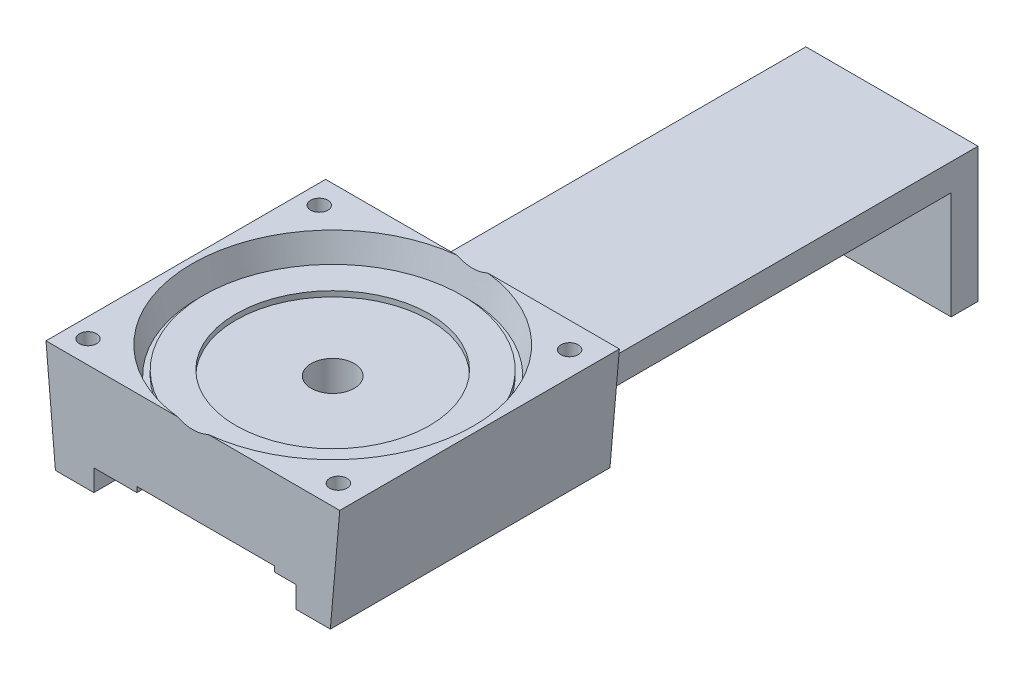
SolidWorks part; units mm, degrees
material "1060 Alloy"
ref_plane "Front Plane" through (0, 0, 0) normal (0, 0, 1) x (1, 0, 0)
ref_plane "Top Plane" through (0, 0, 0) normal (0, 1, 0) x (1, 0, 0)
ref_plane "Right Plane" through (0, 0, 0) normal (1, 0, 0) x (0, 0, -1)
sketch "Sketch1" plane through (0, 0, 0) normal (0, 1, 0) x (1, 0, 0)
  line L0 (-22.225, 41.275) -> (-41.275, 41.275)
  line L1 (41.275, -41.275) -> (-41.275, -41.275)
  line L2 (41.275, -41.275) -> (41.275, 41.275)
  line L3 (41.275, 41.275) -> (28.575, 41.275)
  line L4 (-41.275, -41.275) -> (-41.275, 41.275)
  line L5 (41.275, -41.275) -> (-41.275, 41.275) construction
  line L6 (41.275, 41.275) -> (-41.275, -41.275) construction
  line L8 (-22.225, 41.275) -> (-22.225, 161.925)
  line L9 (-22.225, 161.925) -> (28.575, 161.925)
  line L10 (28.575, 41.275) -> (28.575, 161.925)
  point P0 (0, 0)
  dimension "D1" = 82.55
  dimension "D2" = 82.55
  dimension "D3" = 50.8
  dimension "D4" = 12.7
  dimension "D5" = 203.2
extrude "Boss-Extrude1" add sketch "Sketch1" against normal blind 7.9375
sketch "Sketch2" plane through (0, -7.9375, 0) normal (0, -1, 0) x (1, 0, 0)
  line L0 (28.575, -41.275) -> (28.575, -161.925) construction
  line L1 (-22.225, -161.925) -> (28.575, -161.925)
  line L2 (-22.225, -161.925) -> (-22.225, -153.9875)
  line L3 (-22.225, -153.9875) -> (28.575, -153.9875)
  line L4 (28.575, -161.925) -> (28.575, -153.9875)
  dimension "D1" = 7.9375
extrude "Boss-Extrude2" add sketch "Sketch2" along normal blind 31.75
sketch "Sketch8" plane through (0, 0, 0) normal (0, 1, 0) x (1, 0, 0)
  line L1 (-41.275, -41.275) -> (41.275, -41.275)
  line L2 (-41.275, -41.275) -> (-41.275, 41.275)
  line L3 (-41.275, 41.275) -> (41.275, 41.275)
  line L4 (41.275, -41.275) -> (41.275, 41.275)
extrude "Boss-Extrude6" add sketch "Sketch8" along normal blind 7.9375
sketch "Sketch3" plane through (0, -7.9375, 0) normal (0, -1, 0) x (1, 0, 0)
  line L0 (-22.225, -41.275) -> (-41.275, -41.275) construction
  line L1 (-41.275, 41.275) -> (-29.0692, 41.275)
  line L2 (-41.275, 41.275) -> (-41.275, -41.275)
  line L3 (-41.275, -41.275) -> (-29.0692, -41.275)
  line L4 (-29.0692, 41.275) -> (-29.0692, -41.275)
  line L6 (41.275, 41.275) -> (28.575, 41.275)
  line L7 (41.275, 41.275) -> (41.275, -41.275)
  line L8 (41.275, -41.275) -> (28.575, -41.275)
  line L9 (28.575, 41.275) -> (28.575, -41.275)
extrude "Boss-Extrude3" [suppressed] add sketch "Sketch3" along normal blind 7.9375
sketch "Sketch4" plane through (0, 0, 0) normal (0, 1, 0) x (1, 0, 0)
  circle A0 centre (0, 0) radius 6.35
  dimension "D1" = 12.7
extrude "Cut-Extrude1" [suppressed] cut sketch "Sketch4" against normal through all
sketch "Sketch5" [suppressed] plane through (0, -7.9375, 0) normal (0, -1, 0) x (1, 0, 0)
  line L1 (-29.0692, 41.275) -> (-16.3692, 41.275)
  line L2 (-29.0692, 41.275) -> (-29.0692, -41.275)
  line L3 (-29.0692, -41.275) -> (-16.3692, -41.275)
  line L4 (-16.3692, 41.275) -> (-16.3692, -41.275)
  line L5 (28.575, 41.275) -> (22.225, 41.275)
  line L6 (28.575, 41.275) -> (28.575, -41.275)
  line L7 (28.575, -41.275) -> (22.225, -41.275)
  line L8 (22.225, 41.275) -> (22.225, -41.275)
  dimension "D1" = 12.7
  dimension "D2" = 82.55
  dimension "D3" = 6.35
  dimension "D4" = 82.55
extrude "Boss-Extrude4" [suppressed] add sketch "Sketch5" along normal blind 1.5875
sketch "Sketch6" plane through (0, 0, 0) normal (0, 1, 0) x (1, 0, 0)
  circle A0 centre (0, 0) radius 28.575
  circle A1 centre (0, 0) radius 38.1
  dimension "D1" = 57.15
  dimension "D2" = 76.2
extrude "Boss-Extrude5" [suppressed] add sketch "Sketch6" along normal blind 1.5875
draft "Draft1" [suppressed] type of draft neutral plane draft angle 5 neutral plane "Top Plane" faces to draft 4 parameters "D1"=5
draft "Draft2" [suppressed] type of draft neutral plane draft angle 5 faces to draft 1 parameters "D1"=5
sketch "Sketch9" plane through (0, -7.9375, 0) normal (0, -1, 0) x (-1, 0, 0)
  line L0 (41.275, 41.275) -> (-41.275, 41.275) construction
  line L1 (-41.275, 41.275) -> (-41.275, -41.275) construction
  line L2 (-41.275, -41.275) -> (41.275, -41.275) construction
  line L3 (41.275, -41.275) -> (41.275, 41.275) construction
  line L4 (41.275, 41.275) -> (-41.275, 41.275)
  line L5 (-41.275, 41.275) -> (-41.275, -41.275)
  line L6 (-41.275, -41.275) -> (41.275, -41.275)
  line L7 (41.275, -41.275) -> (41.275, 41.275)
sketch "Sketch10" plane through (0, 7.9375, 0) normal (0, 1, 0) x (1, 0, 0)
  circle A0 centre (0, 0) radius 6.35
  dimension "D1" = 12.7
extrude "Center Hole" cut sketch "Sketch10" against normal up to surface (15.875 mm away) up to face at (1.5875, -7.9375, -48.8156)
sketch "Sketch12" plane through (0, -7.9375, 0) normal (0, -1, 0) x (1, 0, 0)
  line L0 (-41.275, -41.275) -> (41.275, -41.275) construction
  line L1 (-41.275, 41.275) -> (-29.2318, 41.275)
  line L2 (-41.275, 41.275) -> (-41.275, -41.275)
  line L3 (-41.275, -41.275) -> (-29.2318, -41.275)
  line L4 (-29.2318, 41.275) -> (-29.2318, -41.275)
  line L6 (41.275, 41.275) -> (30.384, 41.275)
  line L7 (41.275, 41.275) -> (41.275, -41.275)
  line L8 (41.275, -41.275) -> (30.384, -41.275)
  line L9 (30.384, 41.275) -> (30.384, -41.275)
extrude "Clamp Pad" add sketch "Sketch12" along normal blind 7.9375
sketch "Sketch13" plane through (0, -7.9375, 0) normal (0, -1, 0) x (1, 0, 0)
  line L0 (-41.275, -41.275) -> (41.275, -41.275) construction
  line L1 (-29.2318, 41.275) -> (-16.5318, 41.275)
  line L2 (-29.2318, 41.275) -> (-29.2318, -41.275)
  line L3 (-29.2318, -41.275) -> (-16.5318, -41.275)
  line L4 (-16.5318, 41.275) -> (-16.5318, -41.275)
  line L6 (30.384, 41.275) -> (24.034, 41.275)
  line L7 (30.384, 41.275) -> (30.384, -41.275)
  line L8 (30.384, -41.275) -> (24.034, -41.275)
  line L9 (24.034, 41.275) -> (24.034, -41.275)
  dimension "D1" = 12.7
  dimension "D2" = 6.35
extrude "Wear Pad" add sketch "Sketch13" along normal blind 1.5875
sketch "Sketch14" plane through (0, 7.9375, 0) normal (0, 1, 0) x (1, 0, 0)
  line L1 (-41.275, 41.275) -> (41.275, 41.275)
  line L2 (-41.275, 41.275) -> (-41.275, -41.275)
  line L3 (-41.275, -41.275) -> (41.275, -41.275)
  line L4 (41.275, 41.275) -> (41.275, -41.275)
extrude "Boss-Extrude10" add sketch "Sketch14" along normal blind 7.9375
sketch "Sketch15" plane through (0, 15.875, 0) normal (0, 1, 0) x (1, 0, 0)
  circle A0 centre (0, 0) radius 39.6875
  dimension "D1" = 79.375
extrude "Cut-Extrude3" cut sketch "Sketch15" against normal blind 7.9375
sketch "Sketch11" plane through (0, 7.9375, 0) normal (0, 1, 0) x (1, 0, 0)
  circle A0 centre (0, 0) radius 28.575
  circle A1 centre (0, 0) radius 38.1
  dimension "D1" = 57.15
  dimension "D2" = 76.2
extrude "Boss-Extrude7" add sketch "Sketch11" along normal blind 1.5875
ref_plane "Plane1" through (0, 9.525, 0) normal (0, 1, 0) x (1, 0, 0)
sketch "Sketch17" plane through (0, 7.9375, 0) normal (0, 1, 0) x (1, 0, 0)
  line L0 (0, 0) -> (0, -39.6875) construction
  circle A0 centre (0, 0) radius 39.6875 construction
sketch "Sketch18" plane through (0, 0, 0) normal (1, 0, 0) x (0, 0, -1)
  point P0 (-39.6875, 7.9375)
sketch "Sketch19" plane through (0, 0, 0) normal (1, 0, 0) x (0, 0, -1)
  line L0 (-39.6875, 7.9375) -> (-39.6875, 15.875)
  line L1 (-39.6875, 15.875) -> (-41.5201, 15.875)
  line L2 (-41.5201, 15.875) -> (-39.6875, 7.9375)
ref_axis "Axis1" through (0, 18.6531, 0) along (0, -1, 0)
revolve "Cut-Revolve1" cut sketch "Sketch19" angle 360 about axis through (0, 18.6531, 0) along (0, -1, 0)
ref_plane "Parting Plane" through (0, -7.9375, 0) normal (0, -1, 0) x (-1, 0, 0)
draft "Draft3" type of draft neutral plane draft angle 5 neutral plane "Parting Plane" faces to draft 2 face at (41.275, 5.1504, 0.3366) face at (-41.275, 5.1504, -0.3366) neutral plane through (0, -7.9375, 0) neutral plane normal (0, -1, 0) parameters "D1"=5
hole_wizard "1/4-20 Tapped Hole1" positions "Sketch20" profile "Sketch21" tap size "1/4-20" standard "ANSI Inch"
sketch "Sketch20" plane through (0, 15.875, 0) normal (0, 1, 0) x (1, 0, 0)
  point P0 (36.2036, -34.5374)
  point P2 (36.2036, 33.7297)
  point P4 (-37.6923, 33.7297)
  point P6 (-37.6923, -34.5374)
sketch "Sketch21" plane through (36.2036, 15.875, 34.5374) normal (1, 0, 0) x (0, 0, 1)
  line L0 (0, 0) -> (0, 14.2338)
  line L1 (0, 14.2338) -> (2.5527, 12.7)
  line L2 (2.5527, 12.7) -> (2.5527, 0)
  line L5 (2.5527, 0) -> (0, 0)
  line L10 (0, 14.2338) -> (-2.5527, 12.7) construction
  line L11 (0, -6.35) -> (0, 107.95) construction
  dimension "Tap Drill Dia." = 5.1054
  dimension "Tap Drill Depth" = 12.7
  dimension "Drill Angle" = 118
cosmetic thread "Hole Thread1" parameters "D1"=15.875, "D2"=6.35
cosmetic thread "Hole Thread2" parameters "D1"=15.875, "D2"=6.35
cosmetic thread "Hole Thread3" parameters "D1"=15.875, "D2"=6.35
cosmetic thread "Hole Thread4" parameters "D1"=15.875, "D2"=6.35
hole_wizard "1/4-20 Tapped Hole2" positions "Sketch22" profile "Sketch23" tap size "1/4-20" standard "ANSI Inch" end condition up to next
sketch "Sketch22" plane through (0, 0, -161.925) normal (0, 0, -1) x (-1, 0, 0)
  point P0 (-4.984, -22.225)
  point P5 (-4.984, -22.225)
sketch "Sketch23" plane through (4.984, -22.225, -161.925) normal (1, 0, 0) x (0, 1, 0)
  line L0 (0, 0) -> (0, 7.9375)
  line L1 (0, 7.9375) -> (2.5527, 7.9375)
  line L2 (2.5527, 7.9375) -> (2.5527, 0)
  line L5 (2.5527, 0) -> (0, 0)
  line L11 (0, -6.35) -> (0, 107.95) construction
  dimension "Thru Tap Drill Dia." = 5.1054
  dimension "Thru Tap Drill Depth" = 7.9375
cosmetic thread "Hole Thread5" parameters "D2"=6.35
